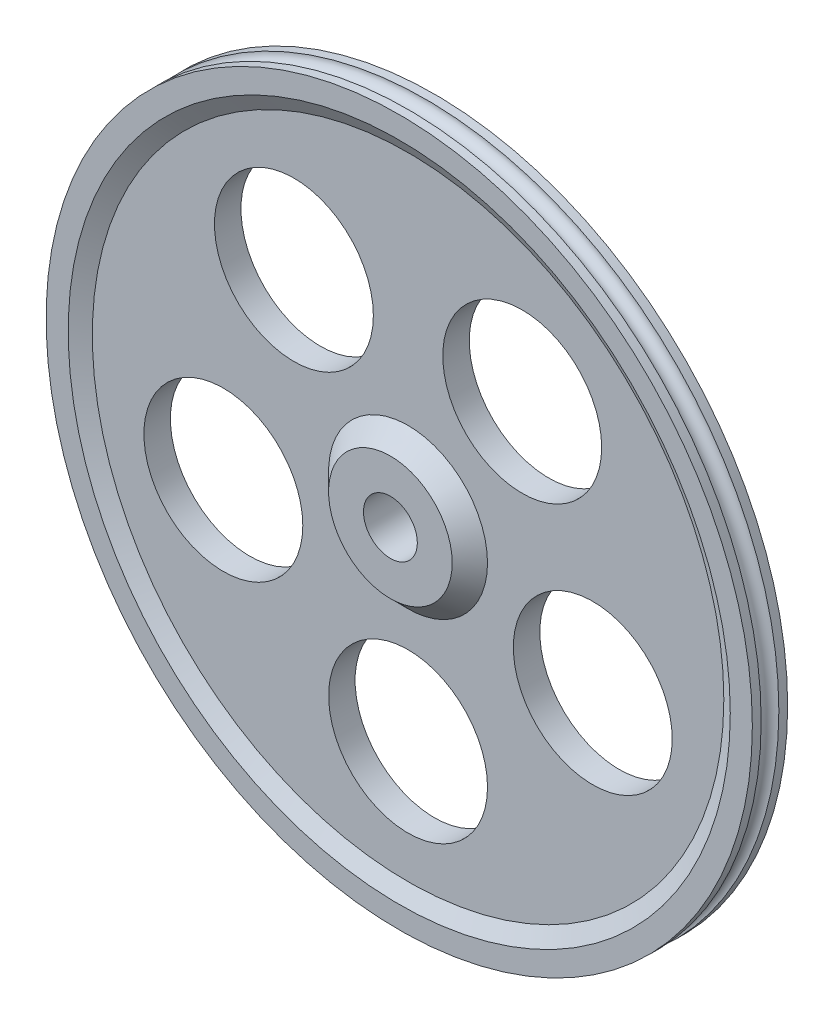
SolidWorks part; units mm, degrees
ref_plane "Front Plane" through (0, 0, 0) normal (0, 0, 1) x (1, 0, 0)
ref_plane "Top Plane" through (0, 0, 0) normal (0, 1, 0) x (1, 0, 0)
ref_plane "Right Plane" through (0, 0, 0) normal (1, 0, 0) x (0, 0, -1)
sketch "Sketch2" plane through (0, 0, 0) normal (0, 1, 0) x (1, 0, 0)
  line L0 (0, 0) -> (64.1086, 0) construction
  line L1 (0, -2) -> (0, -3)
  line L2 (40, -2) -> (0, -2)
  line L3 (40, -2) -> (40, 2)
  line L4 (40, 2) -> (0, 2)
  line L5 (0, -2) -> (0, 2)
  line L6 (40, -2) -> (0, 2) construction
  line L7 (40, 2) -> (0, -2) construction
  line L8 (0, -3) -> (7, -3)
  line L9 (7, -3) -> (7, -1)
  line L10 (7, -1) -> (35.7679, -1)
  line L11 (35.7679, -1) -> (37.5, -2)
  circle A0 centre (40, 0) radius 1
  point P3 (20, 0)
  point P15 (0, 0)
  dimension "D3" = 2
  dimension "D1" = 4
  dimension "D2" = 40
  dimension "D4" = 7
  dimension "D5" = 1
  dimension "D6" = 2.5
  dimension "D7" = 30
  dimension "D8" = 5
revolve "Revolve1" add sketch "Sketch2" angle 360 about L5 region at (3.5, 0, 2.5) region at (19.3422, 0, -0.3462)
sketch "Sketch3" plane through (0, 0, 3) normal (0, 0, 1) x (1, 0, 0)
  circle A0 centre (0, 0) radius 3.05
  dimension "D1" = 6.1
extrude "Cut-Extrude1" cut sketch "Sketch3" against normal through all
chamfer "Chamfer1" distance 2 angle 45 1 edges at (7, 0, 1)
sketch "Sketch4" plane through (0, 0, 1) normal (0, 0, 1) x (1, 0, 0)
  line L0 (0, 0) -> (0, -35.7679) construction
  circle A0 centre (0, 0) radius 35.7679 construction
  circle A1 centre (0, -22) radius 9
  circle A2 centre (-20.9232, -6.7984) radius 9
  circle A3 centre (-12.9313, 17.7984) radius 9
  circle A4 centre (12.9313, 17.7984) radius 9
  circle A5 centre (20.9232, -6.7984) radius 9
  point P18 (0, 0)
  dimension "D1" = 18
  dimension "D2" = 22
  dimension "D3" = 5
extrude "Cut-Extrude2" cut sketch "Sketch4" against normal through all
